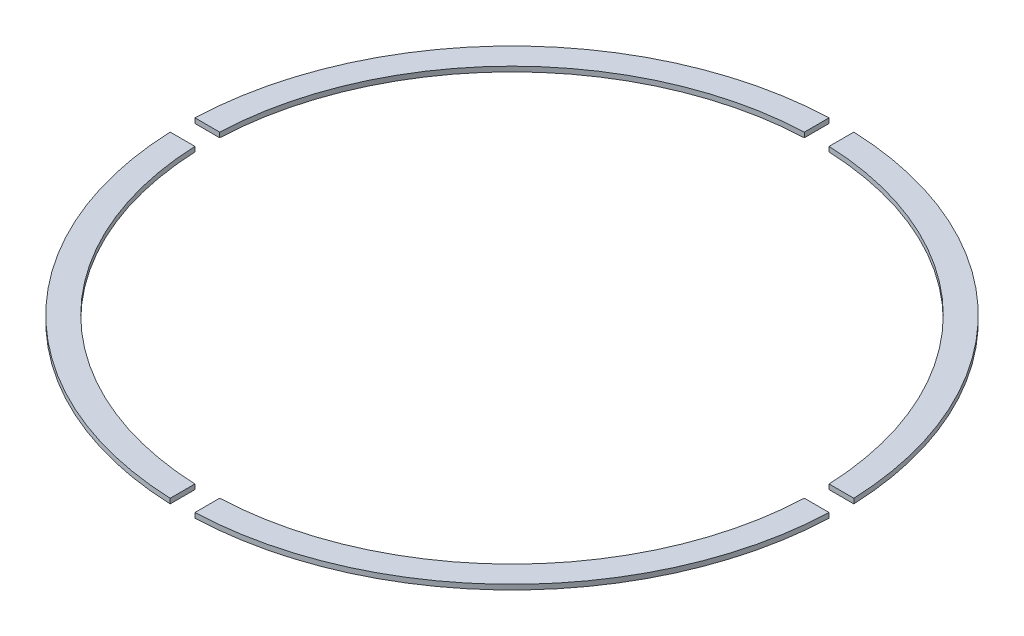
SolidWorks part; units mm, degrees
ref_plane "Front Plane" through (0, 0, 0) normal (0, 0, 1) x (1, 0, 0)
ref_plane "Top Plane" through (0, 0, 0) normal (0, 1, 0) x (1, 0, 0)
ref_plane "Right Plane" through (0, 0, 0) normal (1, 0, 0) x (0, 0, -1)
sketch "Sketch1" plane through (0, 0, 0) normal (0, 1, 0) x (1, 0, 0)
  line L0 (185, 0) -> (-185, 0) construction
  circle A0 centre (0, 0) radius 185
  circle A1 centre (0, 0) radius 200
  dimension "D1" = 370
  dimension "D2" = 400
extrude "Boss-Extrude1" add sketch "Sketch1" along normal mid plane 3
sketch "Sketch2" plane through (0, 0, 0) normal (0, 1, 0) x (1, 0, 0)
  line L1 (157.6447, 7.5) -> (227.3553, 7.5)
  line L2 (157.6447, 7.5) -> (157.6447, -7.5)
  line L3 (157.6447, -7.5) -> (227.3553, -7.5)
  line L4 (227.3553, 7.5) -> (227.3553, -7.5)
  line L5 (157.6447, 7.5) -> (227.3553, -7.5) construction
  line L6 (157.6447, -7.5) -> (227.3553, 7.5) construction
  circle A0 centre (0, 0) radius 192.5 construction
  circle A1 centre (0, 0) radius 185 construction
  point P5 (192.5, 0)
  dimension "D1" = 7.5
  dimension "D2" = 15
extrude "Cut-Extrude1" cut sketch "Sketch2" against normal through all and the other way through all
sketch "Sketch4" plane through (0, 0, 0) normal (1, 0, 0) x (0, 0, -1)
  line L0 (0, 167.5) -> (0, -167.5) construction
  dimension "D1" = 335
pattern_circular "CirPattern1" count 4 every 90 about axis through (0, 167.5, 0) along (0, -1, 0) of "Cut-Extrude1" reverse direction yes
sketch "Sketch5" plane through (0, 0, 0) normal (0, 1, 0) x (1, 0, 0)
  line L0 (0, 250) -> (0, -250) construction
  dimension "D1" = 500
